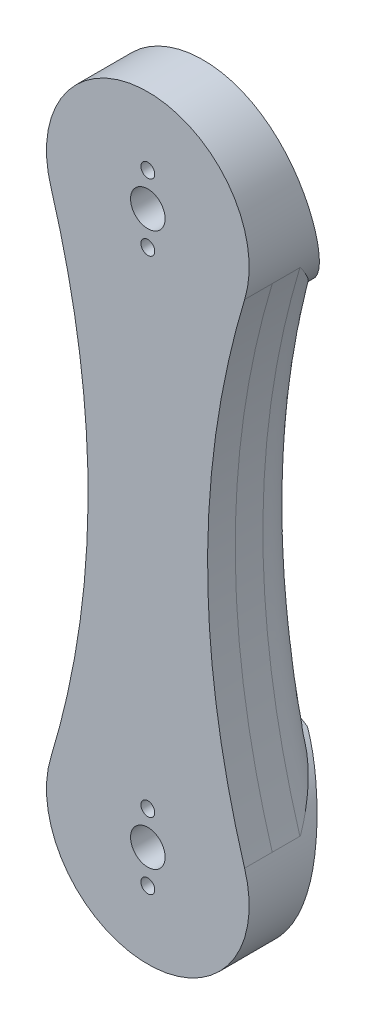
SolidWorks part; units mm, degrees
note: The reader was unsure of these and kept them because the rebuilt part matched: shared geometry of "Sketch3<11>".
ref_plane "Front Plane" through (0, 0, 0) normal (0, 0, 1) x (1, 0, 0)
ref_plane "Top Plane" through (0, 0, 0) normal (0, 1, 0) x (1, 0, 0)
ref_plane "Right Plane" through (0, 0, 0) normal (1, 0, 0) x (0, 0, -1)
sketch "Sketch3" plane through (0, 0, 0) normal (0, 0, 1) x (1, 0, 0)
  line L0 (0, 0) -> (0, 120) construction
  line L3 (-21, 113.4426) -> (21, 113.4426)
  line L4 (-21, 6.5574) -> (21, 6.5574)
  circle A0 centre (0, 0) radius 22
  circle A1 centre (0, 120) radius 22
  spline S0 degree 2 poles (-21, 113.4426) (-4.9381, 59.8501) (-21, 6.5574) knots 0 0 0 1 1 1
  spline S1 degree 2 poles (21, 113.4426) (4.9381, 59.8501) (21, 6.5574) knots 0 0 0 1 1 1
  dimension "D1" = 44
  dimension "D7" = 21
  dimension "D2" = 120
  dimension "D3" = 21
  dimension "D4" = 21
  dimension "D5" = 13
  dimension "D6" = 21
  dimension "D8" = 13
  dimension "D9" = 56.8348
extrude "Boss-Extrude5" add sketch "Sketch3" along normal blind 16 contours L4 S1 L3 S0
extrude "Boss-Extrude6" add sketch "Sketch3<11>" along normal blind 22 contours A1 | A0
sketch "Sketch3<11>" plane through (0, 0, 0) normal (0, 0, 1) x (1, 0, 0) same geometry as "Sketch3"
sketch "Sketch9" plane through (0, 0, 0) normal (1, 0, 0) x (0, 0, -1)
  line L1 (0, -22) -> (0, 6.5574) construction
  line L3 (-10, -22) -> (-10, 142) construction
  line L4 (0, 142) -> (-10, 142)
  line L5 (0, 142) -> (-22, 142) construction
  line L6 (-22, -22) -> (0, -22) construction
  line L7 (4.3935, 38.6259) -> (-17.2608, -42.189) construction
  line L8 (0, -22) -> (-10, -22)
  line L9 (0, -22) -> (0, 18)
  line L10 (0, 142) -> (0, 102)
  spline S0 degree 3 poles (-10, -22) (-10, -8.2113) (-9.1407, 6.5468) (0, 18) knots 0 0 0 0 1 1 1 1
  spline S1 degree 3 poles (-10, 142) (-10, 128.2563) (-8.08, 113.7402) (0, 102) knots 0 0 0 0 1 1 1 1
  point P9 (13.4569, -8.0249)
  point P16 (-8.1938, 0)
  dimension "D5" = 40
  dimension "D6" = 122
  dimension "D1" = 8.1938
  dimension "D4" = 8.19
  dimension "D2" = 40
  dimension "D3" = 10
fillet "Fillet1" radius 10 2 edges
ref_plane "Plane1" through (0, 0, 16) normal (0, 0, 1) x (1, 0, 0)
sketch "Sketch10" plane through (0, 0, 16) normal (0, 0, 1) x (1, 0, 0)
  arc A2 (-21, 113.4426) -> (21, 113.4426) centre (0, 120) ccw
  arc A3 (21, 6.5574) -> (-21, 6.5574) centre (0, 0) ccw
  arc A4 (-21, 113.4426) -> (21, 113.4426) centre (0, 120) ccw
  arc A5 (21, 6.5574) -> (-21, 6.5574) centre (0, 0) ccw
  parabola Q2 (21, 6.5574) -> (21, 113.4426) focus (101.8707, 59.0957) apex (12.9768, 58.2663)
  parabola Q3 (-21, 113.4426) -> (-21, 6.5574) focus (-101.8707, 59.0957) apex (-12.9768, 58.2663)
  parabola Q4 (21, 6.5574) -> (21, 113.4426) focus (101.8707, 59.0957) apex (12.9768, 58.2663)
  parabola Q5 (-21, 113.4426) -> (-21, 6.5574) focus (-101.8707, 59.0957) apex (-12.9768, 58.2663)
  dimension "D1" = 0
extrude "Boss-Extrude7" add sketch "Sketch10" along normal up to surface (6 mm away) up to face at (22, 120, 22)
extrude "Cut-Extrude8" cut sketch "Sketch9" against normal through all both and the other way through all
sketch "Sketch13" plane through (0, 0, 0) normal (0, 1, 0) x (1, 0, 0)
  line L0 (0, -9.5) -> (0, -0.3927) construction
  circle A0 centre (0, -9.5) radius 5.75
  dimension "D1" = 11.5
  dimension "D2" = 9.5
extrude "Cut-Extrude9" cut sketch "Sketch13" against normal blind 0.01 and the other way blind 126
sketch "Sketch14" plane through (0, 0, 16) normal (0, 0, 1) x (1, 0, 0)
  arc A10 (19.0909, 114.0387) -> (-19.0909, 114.0387) centre (0, 120) ccw
  circle A11 centre (0, 120) radius 20
  arc A13 (-19.0909, 5.9613) -> (19.0909, 5.9613) centre (0, 0) ccw
  circle A14 centre (0, 0) radius 20
  point P0 (18.1364, 112.6669)
  dimension "D1" = 2
  dimension "D2" = 2
extrude "Cut-Extrude10" cut sketch "Sketch14" against normal blind 30
sketch "Sketch17" plane through (0, 0, 16) normal (0, 0, -1) x (-1, 0, 0)
  line L0 (0, 7.25) -> (0, -7.25) construction
  line L1 (0, 0) -> (0, 120) construction
  line L2 (0, 60) -> (81.3356, 60) construction
  circle A0 centre (0, 0) radius 3.75
  circle A1 centre (0, -7.25) radius 1.5
  circle A2 centre (0, 7.25) radius 1.5
  circle A3 centre (0, 112.75) radius 1.5
  circle A4 centre (0, 120) radius 3.75
  circle A5 centre (0, 127.25) radius 1.5
  dimension "D1" = 7.5
  dimension "D2" = 3
  dimension "D3" = 3
  dimension "D4" = 7.25
extrude "Cut-Extrude11" cut sketch "Sketch17" against normal through all both and the other way through all
